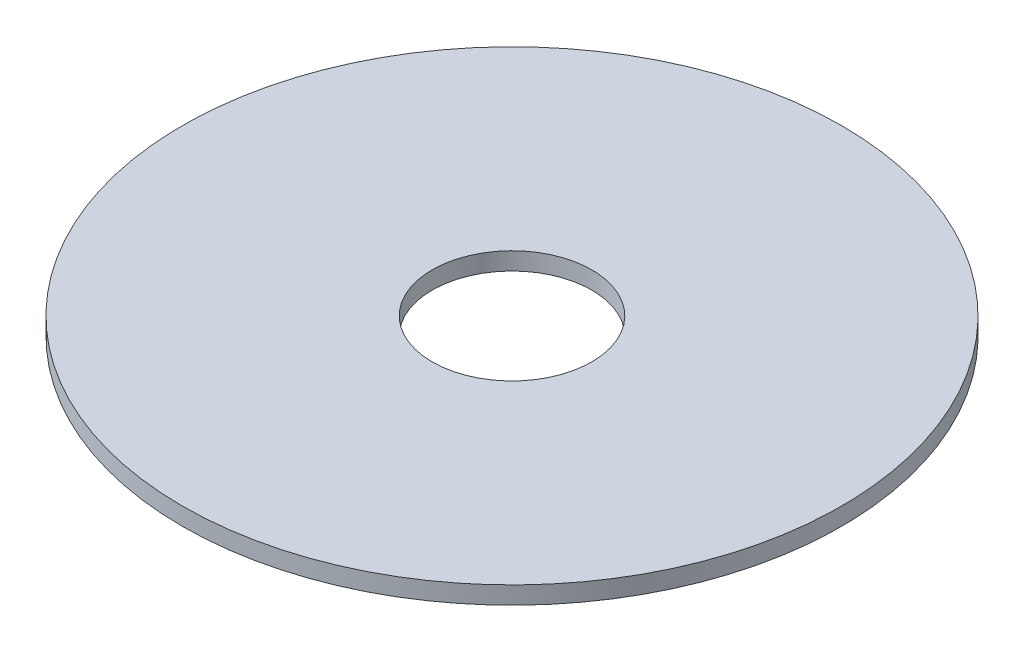
SolidWorks part; units mm, degrees
ref_plane "Front Plane" through (0, 0, 0) normal (0, 0, 1) x (1, 0, 0)
ref_plane "Top Plane" through (0, 0, 0) normal (0, 1, 0) x (1, 0, 0)
ref_plane "Right Plane" through (0, 0, 0) normal (1, 0, 0) x (0, 0, -1)
sketch "Sketch1" plane through (0, 0, 0) normal (0, 1, 0) x (1, 0, 0)
  circle A0 centre (0, 0) radius 93.6962
  circle A1 centre (0, 0) radius 22.684
extrude "Boss-Extrude1" add sketch "Sketch1" along normal blind 2
extrude "Boss-Extrude2" add sketch "Sketch1<3>" along normal blind 5
sketch "Sketch1<3>" plane through (0, 0, 0) normal (0, 1, 0) x (1, 0, 0) same geometry as "Sketch1"
